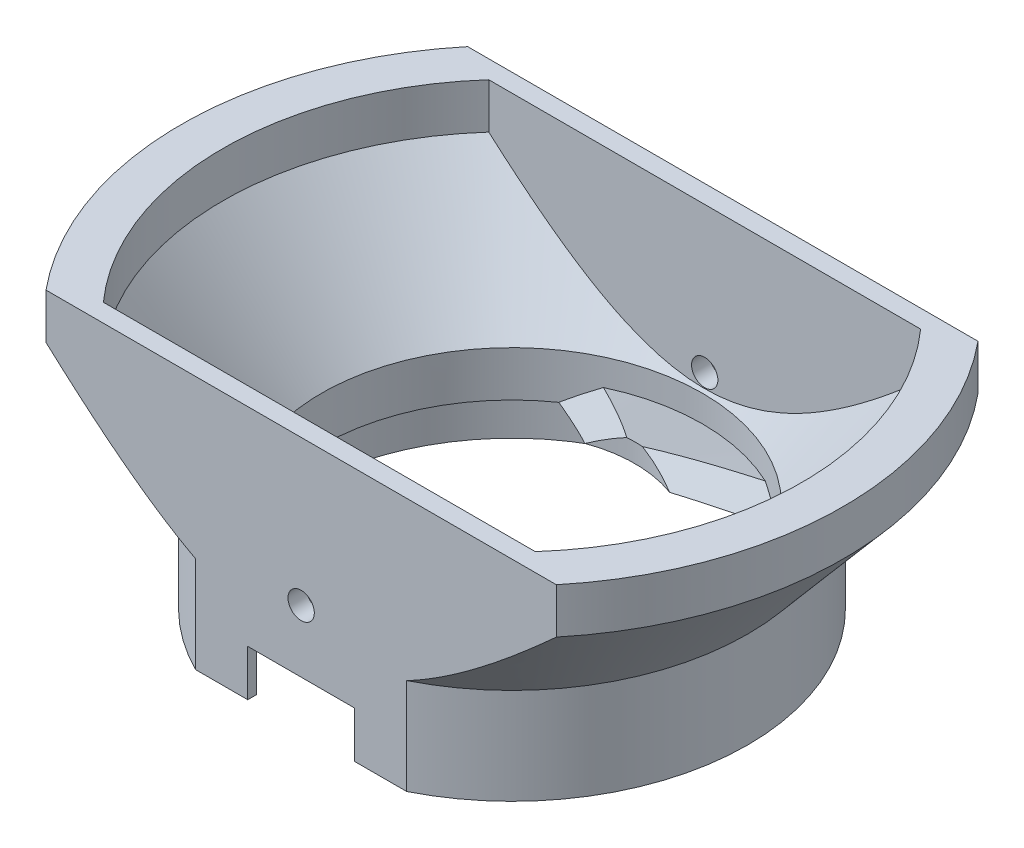
SolidWorks part; units mm, degrees
other "Markup1"
sketch "Sketch12" plane through (-36.5, 26, 23.25) normal (-0.7179, 0.6958, 0.0221) x (0.0006, -0.0311, 0.9995)
ref_plane "Front Plane" through (0, 0, 0) normal (0, 0, 1) x (1, 0, 0)
ref_plane "Top Plane" through (0, 0, 0) normal (0, 1, 0) x (1, 0, 0)
ref_plane "Right Plane" through (0, 0, 0) normal (1, 0, 0) x (0, 0, -1)
sketch "Sketch1" plane through (0, 0, 0) normal (1, 0, 0) x (0, 0, -1)
  line L0 (0, 0) -> (0, 26) construction
  line L1 (-26, 0) -> (-26, 8.5907)
  line L2 (-26, 8.5907) -> (-36.5, 21)
  line L3 (-36.5, 21) -> (-31.9152, 21)
  line L4 (-31.9152, 21) -> (-21, 8.1)
  line L6 (-23.0525, 0) -> (-26, 0)
  line L7 (-23.0525, 0) -> (-23.0525, 3.1)
  line L8 (-36.5, 21) -> (-31.9152, 21)
  line L9 (-36.5, 21) -> (-36.5, 26)
  line L10 (-36.5, 26) -> (-31.9152, 26)
  line L11 (-31.9152, 21) -> (-31.9152, 26)
  line L12 (-23.0525, 3.1) -> (-21, 3.1)
  line L13 (-21, 3.1) -> (-21, 8.1)
  dimension "D1" = 3.5
  dimension "D2" = 26
  dimension "D3" = 23.0525
  dimension "D4" = 36.5
  dimension "D5" = 5
  dimension "D6" = 26
  dimension "D7" = 21
  dimension "D8" = 3.1
  dimension "D9" = 5
revolve "Revolve1" add sketch "Sketch1" angle 360 about L0 region at (0, 10.8751, 26.9281) region at (0, 23.5, 34.2076)
sketch "Sketch2" plane through (0, 0, 0) normal (0, -1, 0) x (1, 0, 0)
  line L1 (-28.1369, -23.25) -> (28.1369, -23.25)
  line L2 (-28.1369, -23.25) -> (-28.1369, -36.5)
  line L3 (-28.1369, -36.5) -> (28.1369, -36.5)
  line L4 (28.1369, -23.25) -> (28.1369, -36.5)
  line L5 (-28.1369, 23.25) -> (28.1369, 23.25)
  line L6 (-28.1369, 23.25) -> (-28.1369, 36.5)
  line L7 (-28.1369, 36.5) -> (28.1369, 36.5)
  line L8 (28.1369, 23.25) -> (28.1369, 36.5)
  circle A0 centre (0, 0) radius 26 construction
  circle A1 centre (0, 0) radius 36.5 construction
  circle A2 centre (0, 0) radius 36.5 construction
  point P5 (0, -23.25)
  dimension "D1" = 23.25
extrude "Cut-Extrude1" cut sketch "Sketch2" against normal through all
sketch "Sketch6" plane through (0, 26, 0) normal (0, 1, 0) x (1, 0, 0)
  line L0 (28.1369, 23.25) -> (-28.1369, 23.25)
  line L1 (-28.1369, 23.25) -> (-28.1369, 21.25)
  line L2 (-28.1369, 21.25) -> (28.1369, 21.25)
  line L3 (28.1369, 21.25) -> (28.1369, 23.25)
  line L5 (-28.1369, -23.25) -> (28.1369, -23.25)
  line L6 (-28.1369, -23.25) -> (-28.1369, -21.25)
  line L7 (-28.1369, -21.25) -> (28.1369, -21.25)
  line L8 (28.1369, -23.25) -> (28.1369, -21.25)
  dimension "D1" = 2
extrude "Boss-Extrude2" add sketch "Sketch6" against normal up to surface (1.0473 mm away) up to face at (0, 15.9992, 0)
sketch "Sketch3" plane through (0, 0, 0) normal (0, -1, 0) x (1, 0, 0)
  line L0 (-11.6378, 23.25) -> (11.6378, 23.25) construction
  line L1 (-5.89, -23.25) -> (5.89, -23.25)
  line L2 (-5.89, -23.25) -> (-5.89, -22.2873)
  line L3 (-5.89, -22.2873) -> (5.89, -22.2873)
  line L4 (5.89, -23.25) -> (5.89, -22.2873)
  line L5 (11.6378, -23.25) -> (-11.6378, -23.25) construction
  line L6 (5.89, 23.25) -> (-5.89, 23.25)
  line L7 (5.89, 23.25) -> (5.89, 22.2873)
  line L8 (5.89, 22.2873) -> (-5.89, 22.2873)
  line L9 (-5.89, 23.25) -> (-5.89, 22.2873)
  circle A0 centre (0, 0) radius 23.0525 construction
  point P6 (0, -22.2873)
  point P16 (0, 22.2873)
  dimension "D1" = 11.78
extrude "Cut-Extrude2" cut sketch "Sketch3" against normal up to surface (3.1 mm away) up to face at (0, 3.1, -21)
ref_plane "Plane1" through (0, 4, 0) normal (0, -1, 0) x (-1, 0, 0)
sketch "Sketch4" plane through (0, 3.1, 0) normal (0, -1, 0) x (-1, 0, 0)
  line L0 (7, 19.799) -> (7, 9.799)
  line L1 (7, 9.799) -> (-7, 9.799)
  line L2 (-7, 9.799) -> (-7, 19.799)
  line L3 (2.7392, -11.7268) -> (-1.0703, -20.9727)
  line L4 (2.7392, -11.7268) -> (-10.2051, -6.3934)
  line L5 (-10.2051, -6.3934) -> (-14.0146, -15.6394)
  line L6 (0, 0) -> (-8, -19.4165) construction
  line L7 (7, 19.799) -> (7, 21.964)
  line L8 (-7, 19.799) -> (-7, 21.964)
  line L9 (-1.0703, -20.9727) -> (-1.8951, -22.9745)
  line L10 (-14.0146, -15.6394) -> (-14.8394, -17.6411)
  circle A0 centre (0, 0) radius 21 construction
  circle A1 centre (0, 0) radius 23.0525
  circle A2 centre (0, 0) radius 23.0525 construction
  point P12 (-3.7329, -9.0601)
  circle M25 centre (0, 0) radius 21
  dimension "D1" = 14
  dimension "D2" = 10
  dimension "D3" = 8
extrude "Boss-Extrude1" [suppressed] add sketch "Sketch4" against normal blind 3 from surface contours L2 L1 L0 M25 starting at plane "Plane1"
mirror "Mirror4" [suppressed] about plane through (0, 0, 0) normal (0, 0, 1)
draft "Draft2" [suppressed] type of draft neutral plane draft angle 50 faces to draft 6 reverse direction yes parameters "D1"=50
fillet "Fillet2" [suppressed] radius 2
sketch "Sketch7" plane through (0, 0, -23.25) normal (0, 0, -1) x (-1, 0, 0)
  line L1 (5.89, 3.1) -> (-5.89, 3.1) construction
  circle A0 centre (0, 9.95) radius 1.45
  dimension "D1" = 2.9
  dimension "D2" = 6.85
extrude "Cut-Extrude3" cut sketch "Sketch7" against normal through all
sketch "Sketch9" plane through (0, 0, 0) normal (1, 0, 0) x (0, 0, -1)
  line L0 (21, 3.1) -> (10.3758, 5.9507)
  line L1 (10.3758, 5.9507) -> (10.8941, 7.8824)
  line L2 (10.8941, 7.8824) -> (21.5183, 5.0317)
  line L3 (21.5183, 5.0317) -> (21, 3.1)
  line L4 (21, 3.1) -> (21, 5.3493) construction
  line L5 (-23.0525, 3.1) -> (23.0525, 3.1) construction
  line L6 (-21, 3.1) -> (21, 3.1) construction
  line L7 (21, 3.1) -> (21, 8.1) construction
  line L8 (21, 3.1) -> (16.054, 3.1) construction
  line L9 (10.8941, 7.8824) -> (21.5183, 8.1)
  line L10 (21.5183, 8.1) -> (21.5183, 5.0317)
  line L11 (21, 8.1) -> (-21, 8.1) construction
  line L12 (0, 0) -> (0, 27.7883) construction
  dimension "D1" = 11
  dimension "D2" = 2
  dimension "D4" = 15.02
revolve "Revolve2" add sketch "Sketch9" angle 70 mid plane about L12 region at (0, 5.4912, -15.9471)
mirror "Mirror3" about plane through (0, 0, 0) normal (0, 0, 1) of "Revolve2"
ref_plane "Plane3" through (0, 0, 0) normal (0.9246, 0, -0.381) x (0.381, 0, 0.9246)
sketch "Sketch13" plane through (0, 0, 0) normal (0, -1, 0) x (1, 0, 0)
  line L0 (-5.89, -23.25) -> (-5.89, -22.2873) construction
  line L1 (-5.89, 22.2873) -> (-5.89, 23.25) construction
  line L2 (-5.89, 23.25) -> (-11.6378, 23.25) construction
  line L3 (-11.6378, -23.25) -> (-5.89, -23.25) construction
  line L4 (5.89, -22.2873) -> (5.89, -23.25) construction
  line L5 (5.89, -23.25) -> (11.6378, -23.25) construction
  line L6 (11.6378, 23.25) -> (5.89, 23.25) construction
  line L7 (5.89, 23.25) -> (5.89, 22.2873) construction
  line L8 (-5.89, -23.25) -> (-5.89, -22.2873)
  line L9 (-5.89, 22.2873) -> (-5.89, 23.25)
  line L10 (-5.89, 23.25) -> (-11.6378, 23.25)
  line L11 (-11.6378, -23.25) -> (-5.89, -23.25)
  line L12 (5.89, -22.2873) -> (5.89, -23.25)
  line L13 (5.89, -23.25) -> (11.6378, -23.25)
  line L14 (11.6378, 23.25) -> (5.89, 23.25)
  line L15 (5.89, 23.25) -> (5.89, 22.2873)
  arc A0 (-5.89, 22.2873) -> (-5.89, -22.2873) centre (0, 0) ccw construction
  arc A1 (-11.6378, 23.25) -> (-11.6378, -23.25) centre (0, 0) ccw construction
  arc A2 (11.6378, -23.25) -> (11.6378, 23.25) centre (0, 0) ccw construction
  arc A3 (5.89, -22.2873) -> (5.89, 22.2873) centre (0, 0) ccw construction
  arc A4 (-5.89, 22.2873) -> (-5.89, -22.2873) centre (0, 0) ccw
  arc A5 (-11.6378, 23.25) -> (-11.6378, -23.25) centre (0, 0) ccw
  arc A6 (11.6378, -23.25) -> (11.6378, 23.25) centre (0, 0) ccw
  arc A7 (5.89, -22.2873) -> (5.89, 22.2873) centre (0, 0) ccw
extrude "Boss-Extrude5" add sketch "Sketch13" along normal blind 2
sketch "Sketch16" plane through (0, 3.1, 0) normal (0, -1, 0) x (1, 0, 0)
  circle A0 centre (0, 0) radius 13.25 construction
  circle A1 centre (0, 0) radius 13.55
  dimension "D1" = 26.5
  dimension "D2" = 0.3
extrude "Cut-Extrude6" cut sketch "Sketch16" against normal through all
sketch "Sketch14" [suppressed] plane through (0, 3.1, 0) normal (0, -1, 0) x (1, 0, 0)
  line L32 (-20.4284, 4.8662) -> (-13.5215, 0.8784)
  line L33 (-19.6822, 7.3221) -> (-13.0864, 3.514)
  line L42 (-7.5215, 11.2707) -> (-14.4284, 15.2585)
  line L43 (-9.5864, 9.5762) -> (-16.1822, 13.3842)
  line L52 (-12.9904, 7.5) -> (-18.1865, 10.5) construction
  line L53 (-16.3843, 5.418) -> (-12.8843, 11.4802) construction
  line L62 (-14.7404, 4.4689) -> (-11.2404, 10.5311)
  line L63 (-6, 20.1246) -> (-6, 12.1492)
  line L72 (-3.5, 20.7063) -> (-3.5, 13.0902)
  line L73 (6, 12.1492) -> (6, 20.1246)
  line L82 (3.5, 13.0902) -> (3.5, 20.7063)
  line L83 (-3.5, 15) -> (3.5, 15)
  line L84 (0, 15) -> (0, 21) construction
  line L85 (-3.5, 16.8982) -> (3.5, 16.8982) construction
  line L86 (14.4284, 15.2585) -> (7.5215, 11.2707)
  line L87 (16.1822, 13.3842) -> (9.5864, 9.5762)
  line L88 (13.5215, 0.8784) -> (20.4284, 4.8662)
  line L89 (13.0864, 3.514) -> (19.6822, 7.3221)
  line L90 (11.2404, 10.5311) -> (14.7404, 4.4689)
  line L91 (12.9904, 7.5) -> (18.1865, 10.5) construction
  line L92 (12.8843, 11.4802) -> (16.3843, 5.418) construction
  line L93 (20.4284, -4.8662) -> (13.5215, -0.8784)
  line L94 (19.6822, -7.3221) -> (13.0864, -3.514)
  line L95 (7.5215, -11.2707) -> (14.4284, -15.2585)
  line L96 (9.5864, -9.5762) -> (16.1822, -13.3842)
  line L97 (14.7404, -4.4689) -> (11.2404, -10.5311)
  line L98 (12.9904, -7.5) -> (18.1865, -10.5) construction
  line L99 (16.3843, -5.418) -> (12.8843, -11.4802) construction
  line L100 (6, -20.1246) -> (6, -12.1492)
  line L101 (3.5, -20.7063) -> (3.5, -13.0902)
  line L102 (-6, -12.1492) -> (-6, -20.1246)
  line L103 (-3.5, -13.0902) -> (-3.5, -20.7063)
  line L104 (3.5, -15) -> (-3.5, -15)
  line L105 (0, -15) -> (0, -21) construction
  line L106 (3.5, -16.8982) -> (-3.5, -16.8982) construction
  line L107 (-14.4284, -15.2585) -> (-7.5215, -11.2707)
  line L108 (-16.1822, -13.3842) -> (-9.5864, -9.5762)
  line L109 (-13.5215, -0.8784) -> (-20.4284, -4.8662)
  line L110 (-13.0864, -3.514) -> (-19.6822, -7.3221)
  line L111 (-11.2404, -10.5311) -> (-14.7404, -4.4689)
  line L112 (-12.9904, -7.5) -> (-18.1865, -10.5) construction
  line L113 (-12.8843, -11.4802) -> (-16.3843, -5.418) construction
  arc A23 (-14.4284, 15.2585) -> (-20.4284, 4.8662) centre (0, 0) ccw construction
  arc A24 (-7.5215, 11.2707) -> (-13.5215, 0.8784) centre (0, 0) ccw construction
  circle A25 centre (0, 0) radius 21 construction
  arc A26 (-7.5215, 11.2707) -> (-13.5215, 0.8784) centre (0, 0) ccw
  arc A27 (-14.4284, 15.2585) -> (-16.1822, 13.3842) centre (0, 0) ccw
  arc A28 (-19.6822, 7.3221) -> (-20.4284, 4.8662) centre (0, 0) ccw
  arc A29 (6, 12.1492) -> (-6, 12.1492) centre (0, 0) ccw
  arc A30 (6, 20.1246) -> (3.5, 20.7063) centre (0, 0) ccw
  arc A31 (-3.5, 20.7063) -> (-6, 20.1246) centre (0, 0) ccw
  arc A32 (13.5215, 0.8784) -> (7.5215, 11.2707) centre (0, 0) ccw
  arc A33 (20.4284, 4.8662) -> (19.6822, 7.3221) centre (0, 0) ccw
  arc A34 (16.1822, 13.3842) -> (14.4284, 15.2585) centre (0, 0) ccw
  arc A35 (7.5215, -11.2707) -> (13.5215, -0.8784) centre (0, 0) ccw
  arc A36 (14.4284, -15.2585) -> (16.1822, -13.3842) centre (0, 0) ccw
  arc A37 (19.6822, -7.3221) -> (20.4284, -4.8662) centre (0, 0) ccw
  arc A38 (-6, -12.1492) -> (6, -12.1492) centre (0, 0) ccw
  arc A39 (-6, -20.1246) -> (-3.5, -20.7063) centre (0, 0) ccw
  arc A40 (3.5, -20.7063) -> (6, -20.1246) centre (0, 0) ccw
  arc A41 (-13.5215, -0.8784) -> (-7.5215, -11.2707) centre (0, 0) ccw
  arc A42 (-20.4284, -4.8662) -> (-19.6822, -7.3221) centre (0, 0) ccw
  arc A43 (-16.1822, -13.3842) -> (-14.4284, -15.2585) centre (0, 0) ccw
  point P19 (-14.6343, 8.4491)
  point P114 (0, 0)
  dimension "D1" = 7
  dimension "D2" = 6
extrude "Cut-Extrude8" [suppressed] cut sketch "Sketch14" against normal through all
draft "Draft11" type of draft neutral plane draft angle 60 faces to draft 4 face at (9.9085, 5.1349, 14.1509) face at (-9.9085, 5.1349, 14.1509) face at (9.9085, 5.1349, -14.1509) face at (-9.9085, 5.1349, -14.1509) neutral plane through (0, 3.1, 0) neutral plane normal (0, -1, 0) reverse direction yes parameters "D1"=60
